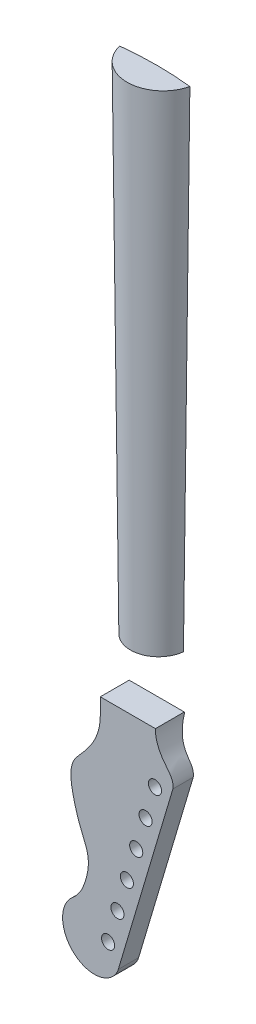
SolidWorks part; units mm, degrees
material "Maple"
ref_plane "Front Plane" through (0, 0, 0) normal (0, 0, 1) x (1, 0, 0)
ref_plane "Top Plane" through (0, 0, 0) normal (0, 1, 0) x (1, 0, 0)
ref_plane "Right Plane" through (0, 0, 0) normal (1, 0, 0) x (0, 0, -1)
sketch "Model" plane through (0, 0, 0) normal (0, 0, 1) x (1, 0, 0)
  line L0 (47.9999, 0) -> (57.149, 660.4)
  line L1 (40.86, 0) -> (46.3494, 660.4)
  line L2 (33.72, 0) -> (35.5498, 660.4)
  line L3 (26.5801, 0) -> (24.7503, 660.4)
  line L4 (19.4401, 0) -> (13.9507, 660.4)
  line L5 (12.3002, 0) -> (3.1511, 660.4)
  line L6 (51.151, 0) -> (60.3001, 660.4)
  line L7 (9.1491, 0) -> (0, 660.4)
  line L8 (51.659, 0) -> (43.9219, 0)
  line L9 (52.1725, 37.0654) -> (44.3327, 37.0654)
  line L10 (52.6572, 72.0505) -> (44.7205, 72.0505)
  line L11 (53.1147, 105.072) -> (45.0865, 105.072)
  line L12 (53.5465, 136.2402) -> (45.4319, 136.2402)
  line L13 (53.954, 165.659) -> (45.7579, 165.659)
  line L14 (54.3387, 193.4267) -> (46.0657, 193.4267)
  line L15 (54.7018, 219.6359) -> (46.3562, 219.6359)
  line L16 (55.0445, 244.3741) -> (46.6304, 244.3741)
  line L17 (55.368, 267.7238) -> (46.8891, 267.7238)
  line L18 (55.6734, 289.763) -> (47.1334, 289.763)
  line L19 (55.9616, 310.5653) -> (47.364, 310.5653)
  line L20 (56.2336, 330.2) -> (47.5816, 330.2)
  line L21 (56.4903, 348.7327) -> (47.787, 348.7327)
  line L22 (56.7327, 366.2252) -> (47.9808, 366.2252)
  line L23 (56.9614, 382.736) -> (48.1638, 382.736)
  line L24 (57.1773, 398.3201) -> (48.3365, 398.3201)
  line L25 (57.3811, 413.0295) -> (48.4996, 413.0295)
  line L26 (57.5734, 426.9133) -> (48.6534, 426.9133)
  line L27 (57.755, 440.0179) -> (48.7987, 440.0179)
  line L28 (57.9263, 452.387) -> (48.9358, 452.387)
  line L29 (58.0881, 464.0619) -> (49.0652, 464.0619)
  line L30 (58.2407, 475.0815) -> (49.1873, 475.0815)
  line L31 (58.3848, 485.4826) -> (49.3026, 485.4826)
  line L32 (58.5208, 495.3) -> (49.4114, 495.3)
  line L33 (44.9379, 0) -> (36.782, 0)
  line L34 (45.3487, 37.0654) -> (36.9874, 37.0654)
  line L35 (45.7365, 72.0505) -> (37.1813, 72.0505)
  line L36 (46.1025, 105.072) -> (37.3643, 105.072)
  line L37 (46.4479, 136.2402) -> (37.537, 136.2402)
  line L38 (46.7739, 165.659) -> (37.7, 165.659)
  line L39 (47.0817, 193.4267) -> (37.8539, 193.4267)
  line L40 (47.3722, 219.6359) -> (37.9991, 219.6359)
  line L41 (47.6464, 244.3741) -> (38.1362, 244.3741)
  line L42 (47.9051, 267.7238) -> (38.2656, 267.7238)
  line L43 (48.1494, 289.763) -> (38.3877, 289.763)
  line L44 (48.38, 310.5653) -> (38.503, 310.5653)
  line L45 (48.5976, 330.2) -> (38.6118, 330.2)
  line L46 (48.803, 348.7327) -> (38.7145, 348.7327)
  line L47 (48.9968, 366.2252) -> (38.8114, 366.2252)
  line L48 (49.1798, 382.736) -> (38.9029, 382.736)
  line L49 (49.3525, 398.3201) -> (38.9893, 398.3201)
  line L50 (49.5156, 413.0295) -> (39.0708, 413.0295)
  line L51 (49.6694, 426.9133) -> (39.1478, 426.9133)
  line L52 (49.8147, 440.0179) -> (39.2204, 440.0179)
  line L53 (49.9518, 452.387) -> (39.2889, 452.387)
  line L54 (50.0812, 464.0619) -> (39.3536, 464.0619)
  line L55 (50.2033, 475.0815) -> (39.4147, 475.0815)
  line L56 (50.3186, 485.4826) -> (39.4723, 485.4826)
  line L57 (50.4274, 495.3) -> (39.5267, 495.3)
  line L58 (37.798, 0) -> (29.6421, 0)
  line L59 (38.0034, 37.0654) -> (29.6421, 37.0654)
  line L60 (38.1973, 72.0505) -> (29.6421, 72.0505)
  line L61 (38.3803, 105.072) -> (29.6421, 105.072)
  line L62 (38.553, 136.2402) -> (29.6421, 136.2402)
  line L63 (38.716, 165.659) -> (29.6421, 165.659)
  line L64 (38.8699, 193.4267) -> (29.6421, 193.4267)
  line L65 (39.0151, 219.6359) -> (29.6421, 219.6359)
  line L66 (39.1522, 244.3741) -> (29.6421, 244.3741)
  line L67 (39.2816, 267.7238) -> (29.6421, 267.7238)
  line L68 (39.4037, 289.763) -> (29.6421, 289.763)
  line L69 (39.519, 310.5653) -> (29.6421, 310.5653)
  line L70 (39.6278, 330.2) -> (29.6421, 330.2)
  line L71 (39.7305, 348.7327) -> (29.6421, 348.7327)
  line L72 (39.8274, 366.2252) -> (29.6421, 366.2252)
  line L73 (39.9189, 382.736) -> (29.6421, 382.736)
  line L74 (40.0053, 398.3201) -> (29.6421, 398.3201)
  line L75 (40.0868, 413.0295) -> (29.6421, 413.0295)
  line L76 (40.1638, 426.9133) -> (29.6421, 426.9133)
  line L77 (40.2364, 440.0179) -> (29.6421, 440.0179)
  line L78 (40.3049, 452.387) -> (29.6421, 452.387)
  line L79 (40.3696, 464.0619) -> (29.6421, 464.0619)
  line L80 (40.4307, 475.0815) -> (29.6421, 475.0815)
  line L81 (40.4883, 485.4826) -> (29.6421, 485.4826)
  line L82 (40.5427, 495.3) -> (29.6421, 495.3)
  line L83 (30.6581, 0) -> (22.5021, 0)
  line L84 (30.6581, 37.0654) -> (22.2967, 37.0654)
  line L85 (30.6581, 72.0505) -> (22.1028, 72.0505)
  line L86 (30.6581, 105.072) -> (21.9199, 105.072)
  line L87 (30.6581, 136.2402) -> (21.7471, 136.2402)
  line L88 (30.6581, 165.659) -> (21.5841, 165.659)
  line L89 (30.6581, 193.4267) -> (21.4302, 193.4267)
  line L90 (30.6581, 219.6359) -> (21.285, 219.6359)
  line L91 (30.6581, 244.3741) -> (21.1479, 244.3741)
  line L92 (30.6581, 267.7238) -> (21.0185, 267.7238)
  line L93 (30.6581, 289.763) -> (20.8964, 289.763)
  line L94 (30.6581, 310.5653) -> (20.7811, 310.5653)
  line L95 (30.6581, 330.2) -> (20.6723, 330.2)
  line L96 (30.6581, 348.7327) -> (20.5696, 348.7327)
  line L97 (30.6581, 366.2252) -> (20.4727, 366.2252)
  line L98 (30.6581, 382.736) -> (20.3812, 382.736)
  line L99 (30.6581, 398.3201) -> (20.2948, 398.3201)
  line L100 (30.6581, 413.0295) -> (20.2133, 413.0295)
  line L101 (30.6581, 426.9133) -> (20.1364, 426.9133)
  line L102 (30.6581, 440.0179) -> (20.0637, 440.0179)
  line L103 (30.6581, 452.387) -> (19.9952, 452.387)
  line L104 (30.6581, 464.0619) -> (19.9305, 464.0619)
  line L105 (30.6581, 475.0815) -> (19.8694, 475.0815)
  line L106 (30.6581, 485.4826) -> (19.8118, 485.4826)
  line L107 (30.6581, 495.3) -> (19.7574, 495.3)
  line L108 (23.5181, 0) -> (15.3622, 0)
  line L109 (23.3127, 37.0654) -> (14.9514, 37.0654)
  line L110 (23.1188, 72.0505) -> (14.5636, 72.0505)
  line L111 (22.9359, 105.072) -> (14.1977, 105.072)
  line L112 (22.7631, 136.2402) -> (13.8522, 136.2402)
  line L113 (22.6001, 165.659) -> (13.5262, 165.659)
  line L114 (22.4462, 193.4267) -> (13.2184, 193.4267)
  line L115 (22.301, 219.6359) -> (12.9279, 219.6359)
  line L116 (22.1639, 244.3741) -> (12.6538, 244.3741)
  line L117 (22.0345, 267.7238) -> (12.395, 267.7238)
  line L118 (21.9124, 289.763) -> (12.1507, 289.763)
  line L119 (21.7971, 310.5653) -> (11.9202, 310.5653)
  line L120 (21.6883, 330.2) -> (11.7025, 330.2)
  line L121 (21.5856, 348.7327) -> (11.4971, 348.7327)
  line L122 (21.4887, 366.2252) -> (11.3033, 366.2252)
  line L123 (21.3972, 382.736) -> (11.1203, 382.736)
  line L124 (21.3108, 398.3201) -> (10.9476, 398.3201)
  line L125 (21.2293, 413.0295) -> (10.7845, 413.0295)
  line L126 (21.1524, 426.9133) -> (10.6307, 426.9133)
  line L127 (21.0797, 440.0179) -> (10.4854, 440.0179)
  line L128 (21.0112, 452.387) -> (10.3483, 452.387)
  line L129 (20.9465, 464.0619) -> (10.2189, 464.0619)
  line L130 (20.8854, 475.0815) -> (10.0968, 475.0815)
  line L131 (20.8278, 485.4826) -> (9.9815, 485.4826)
  line L132 (20.7734, 495.3) -> (9.8727, 495.3)
  line L133 (16.3782, 0) -> (8.6411, 0)
  line L134 (15.9674, 37.0654) -> (8.1276, 37.0654)
  line L135 (15.5796, 72.0505) -> (7.6429, 72.0505)
  line L136 (15.2137, 105.072) -> (7.1854, 105.072)
  line L137 (14.8682, 136.2402) -> (6.7536, 136.2402)
  line L138 (14.5422, 165.659) -> (6.3461, 165.659)
  line L139 (14.2344, 193.4267) -> (5.9614, 193.4267)
  line L140 (13.9439, 219.6359) -> (5.5983, 219.6359)
  line L141 (13.6698, 244.3741) -> (5.2556, 244.3741)
  line L142 (13.411, 267.7238) -> (4.9321, 267.7238)
  line L143 (13.1667, 289.763) -> (4.6267, 289.763)
  line L144 (12.9362, 310.5653) -> (4.3386, 310.5653)
  line L145 (12.7185, 330.2) -> (4.0665, 330.2)
  line L146 (12.5131, 348.7327) -> (3.8098, 348.7327)
  line L147 (12.3193, 366.2252) -> (3.5675, 366.2252)
  line L148 (12.1363, 382.736) -> (3.3387, 382.736)
  line L149 (11.9636, 398.3201) -> (3.1228, 398.3201)
  line L150 (11.8005, 413.0295) -> (2.919, 413.0295)
  line L151 (11.6467, 426.9133) -> (2.7267, 426.9133)
  line L152 (11.5014, 440.0179) -> (2.5451, 440.0179)
  line L153 (11.3643, 452.387) -> (2.3738, 452.387)
  line L154 (11.2349, 464.0619) -> (2.212, 464.0619)
  line L155 (11.1128, 475.0815) -> (2.0594, 475.0815)
  line L156 (10.9975, 485.4826) -> (1.9153, 485.4826)
  line L157 (10.8887, 495.3) -> (1.7793, 495.3)
ref_plane "Plane1" through (0, 37.07, 0) normal (0, 1, 0) x (1, 0, 0)
ref_plane "Plane2" through (0, 413.03, 0) normal (0, 1, 0) x (1, 0, 0)
sketch "Sketch2" plane through (0, 37.07, 0) normal (0, 1, 0) x (1, 0, 0)
  line L0 (22.5021, 0) -> (37.798, 0) construction
  line L4 (30.6581, 0) -> (22.5021, 0) construction
  line L5 (30.6581, 0) -> (22.2967, 0) construction
  line L6 (37.798, 0) -> (29.6421, 0) construction
  line L7 (30.1501, 0) -> (30.1501, -241.3) construction
  line L8 (30.1501, 0) -> (30.1501, -20) construction
  line L9 (30.1501, 0) -> (30.1501, 60) construction
  line L10 (8.7751, 0) -> (51.5251, 0) construction
  arc A0 (51.4416, -0.9412) -> (8.8585, -0.9412) centre (30.1501, -241.3) ccw
  arc A1 (8.7751, 0) -> (8.8585, -0.9412) centre (30.1501, 1.4219) ccw construction
  arc A3 (8.8585, -0.9412) -> (51.4416, -0.9412) centre (30.1501, 1.4219) ccw
  point P17 (30.1501, 0)
  dimension "D1" = 241.3
  dimension "D2" = 20
  dimension "D3" = 60
  dimension "D4" = 42.75
sketch "Sketch4" plane through (0, 413.03, 0) normal (0, 1, 0) x (1, 0, 0)
  line L0 (37.798, 0) -> (22.5021, 0) construction
  line L1 (37.798, 0) -> (29.6421, 0) construction
  line L2 (44.9379, 0) -> (36.782, 0) construction
  line L3 (30.6581, 0) -> (22.5021, 0) construction
  line L4 (30.6581, 0) -> (22.2967, 0) construction
  line L5 (30.1501, 0) -> (30.1501, -241.3) construction
  line L6 (30.1501, 0) -> (30.1501, -22.6) construction
  line L7 (57.2001, 0) -> (3.1001, 0) construction
  circle A0 centre (30.1501, -241.3) radius 241.3 construction
  arc A1 (57.2001, 0) -> (56.8889, -1.4861) centre (30.1501, 4.8875) cw construction
  arc A2 (3.4112, -1.4861) -> (56.8889, -1.4861) centre (30.1501, -241.3) cw
  arc A3 (3.4112, -1.4861) -> (3.1001, 0) centre (30.1501, 4.8875) cw construction
  arc A4 (56.8889, -1.4861) -> (3.4112, -1.4861) centre (30.1501, 4.8875) cw
  point P18 (30.1501, 0)
  dimension "D1" = 241.3
  dimension "D2" = 22.6
  dimension "D3" = 54.1
loft "Loft1" add profiles "Sketch4", "Sketch2" connector at (3.4112, 413.03, 1.4861) connector at (8.8585, 37.07, 0.9412)
sketch "Sketch5" plane through (0, 0, 0) normal (0, 0, 1) x (1, 0, 0)
  line L0 (51.151, 0) -> (51.151, -3.25) construction
  line L1 (51.151, -3.25) -> (9.1491, -3.25) construction
  line L2 (9.1491, -3.25) -> (9.1491, 0) construction
  line L3 (51.151, 0) -> (9.1491, 0) construction
  line L10 (47.9999, 0) -> (47.9999, -42) construction
  line L11 (40.86, 0) -> (40.86, -66) construction
  line L12 (33.72, 0) -> (33.72, -90) construction
  line L13 (26.5801, 0) -> (26.5801, -114) construction
  line L14 (19.4401, 0) -> (19.4401, -138) construction
  line L15 (12.3002, 0) -> (12.3002, -162) construction
  dimension "D1" = 3.25
  dimension "D2" = 42
  dimension "D3" = 66
  dimension "D4" = 90
  dimension "D5" = 114
  dimension "D6" = 138
  dimension "D7" = 162
sketch "Sketch7" plane through (0, 0, 0) normal (0, 0, 1) x (1, 0, 0)
  line L0 (47.9999, -42) -> (50.7999, -42) construction
  line L1 (40.86, -66) -> (43.66, -66) construction
  line L2 (33.72, -90) -> (36.52, -90) construction
  line L3 (26.5801, -114) -> (29.3801, -114) construction
  line L4 (19.4401, -138) -> (22.2401, -138) construction
  line L5 (12.3002, -162) -> (15.1002, -162) construction
  line L6 (50.7999, -42) -> (15.1002, -162) construction
  line L7 (61.8225, -45.2792) -> (26.1228, -165.2792)
  line L8 (61.8225, -45.2792) -> (64.4679, -36.3869)
  line L9 (26.1228, -165.2792) -> (22.17, -178.5661)
  line L10 (9.1491, -3.25) -> (9.1491, -15.8462)
  line L11 (51.151, -3.25) -> (9.1491, -3.25)
  circle A0 centre (50.7999, -42) radius 5
  circle A6 centre (43.66, -66) radius 5
  circle A7 centre (36.52, -90) radius 5
  circle A8 centre (29.3801, -114) radius 5
  circle A9 centre (22.2401, -138) radius 5
  circle A10 centre (15.1002, -162) radius 5
  circle A11 centre (50.7999, -42) radius 7 construction
  circle A12 centre (43.66, -66) radius 7 construction
  circle A13 centre (36.52, -90) radius 7 construction
  circle A14 centre (29.3801, -114) radius 7 construction
  circle A15 centre (22.2401, -138) radius 7 construction
  circle A16 centre (15.1002, -162) radius 7 construction
  arc A17 (-12.1507, -146.4192) -> (-6.0074, -139.1839) centre (-31.6598, -123.629) ccw
  ellipse E0 centre (2.8278, -165.1094) end of major axis (14.6602, -186.0066) minor radius 21.8622 (-12.1507, -146.4192) -> (22.17, -178.5661) ccw
  spline S2 degree 3 poles (51.151, -3.25) (50.9376, -10.7673) (56.4838, -22.0007) (65.2963, -30.5662) (64.4679, -36.3869) knots 0 0 0 0 0.598162 1 1 1 1
  spline S3 degree 3 poles (9.1491, -15.8462) (9.1416, -28.5012) (1.4204, -41.2547) (-15.1493, -58.1713) (-12.0269, -78.7636) (-6.3018, -97.3659) (3.4284, -117.1529) (-3.2556, -134.6457) (-6.0074, -139.1839) knots 0 0 0 0 0.241122 0.31589 0.476811 0.625348 0.735304 0.929975 0.929975 0.929975 0.929975
  point P32 (-6.6579, -142.6678)
  point P33 (0, 0)
  point P37 (-16.1964, -175.8813)
  point P38 (-6.0074, -139.1839)
  dimension "D7" = 10
  dimension "D8" = 10
  dimension "D9" = 10
  dimension "D10" = 10
  dimension "D11" = 10
  dimension "D12" = 10
  dimension "D13" = 11.5
  dimension "D14" = 30
  dimension "D1" = 2.8
  dimension "D2" = 2.8
  dimension "D3" = 2.8
  dimension "D4" = 2.8
  dimension "D5" = 2.8
  dimension "D6" = 2.8
extrude "Boss-Extrude1" add sketch "Sketch7" along normal blind 22 separate body
sketch "Sketch9" plane through (0, 0, 0) normal (1, 0, 0) x (0, 0, -1)
  line L0 (0, -188.6196) -> (-6.5, -188.6196)
  line L1 (-22, -188.6196) -> (0, -188.6196) construction
  line L2 (-6.5, -188.6196) -> (-6.5, -21.6831)
  line L3 (-22, -3.25) -> (0, -3.25) construction
  line L4 (-6.5, -3.25) -> (0, -3.25) construction
  line L6 (0, -3.25) -> (0, -4.75) construction
  line L7 (0, -4.75) -> (-6.5, -21.6831)
  line L8 (-6.5, -21.6831) -> (-6.5, -3.25) construction
  line L9 (0, -4.75) -> (0, -188.6196)
  point P10 (-6.5, -21.6093)
  point P13 (-2.4341, -19.6214)
  point P14 (0, -4.138)
  dimension "D1" = 6.5
  dimension "D2" = 1.5
extrude "Cut-Extrude1" cut sketch "Sketch9" against normal blind 47 and the other way blind 89 contours L9 L7 L2 L0 region at (0, -100.8499, 3.1977)
fillet "Fillet1" radius 35 1 edges at (33.1406, -21.6831, 6.5)
fillet "Fillet2" radius 15 1 edges at (22.17, -178.5661, 14.25)
